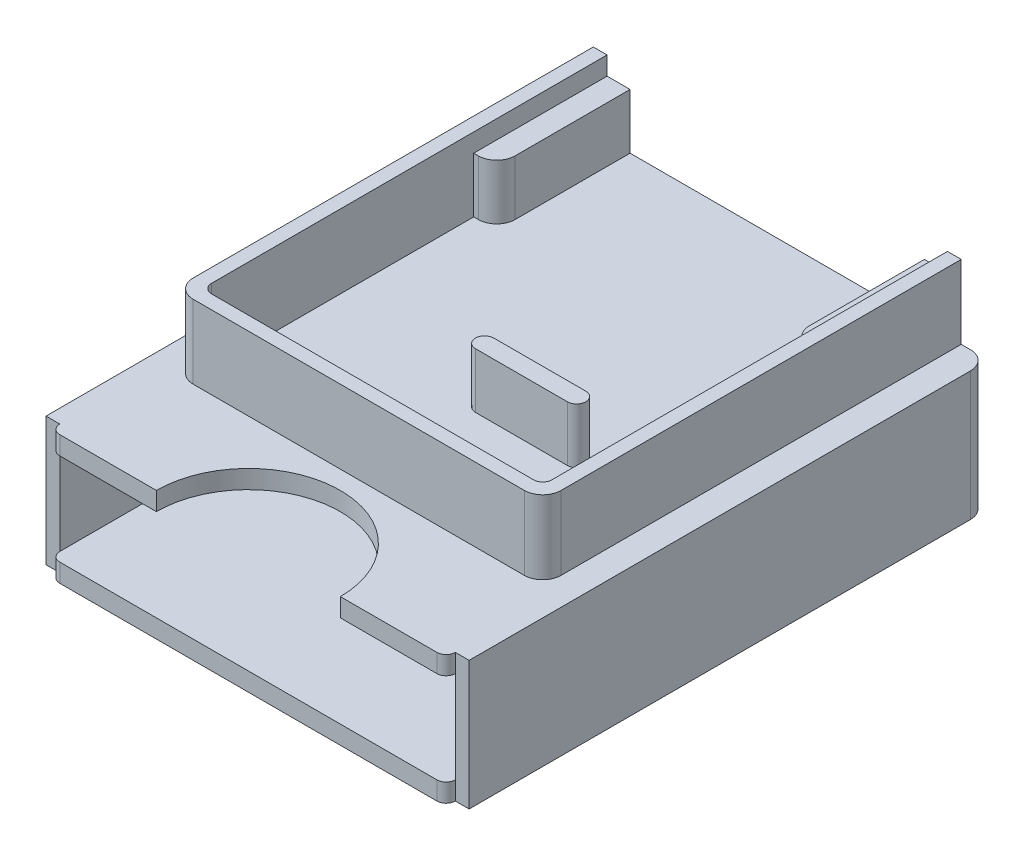
SolidWorks part; units mm, degrees
ref_plane "Front Plane" through (0, 0, 0) normal (0, 0, 1) x (1, 0, 0)
ref_plane "Top Plane" through (0, 0, 0) normal (0, 1, 0) x (1, 0, 0)
ref_plane "Right Plane" through (0, 0, 0) normal (1, 0, 0) x (0, 0, -1)
sketch "Sketch10" plane through (0, 0, 0) normal (0, 1, 0) x (1, 0, 0)
  line L0 (-10.75, -13.5) -> (-11.5, -13.5)
  line L1 (10.5, 14.75) -> (-10.5, 14.75)
  line L2 (11.5, 13.75) -> (11.5, -13.75)
  line L3 (10.5, -14.75) -> (-10.5, -14.75)
  line L4 (-11.5, 13.75) -> (-11.5, -13.75)
  line L5 (4.75, 16.25) -> (-4.75, 16.25)
  line L6 (4.75, 16.25) -> (4.75, 14.75)
  line L7 (10.25, 14) -> (-10.25, 14)
  line L8 (10.75, 13.5) -> (10.75, -13.5)
  line L9 (10.25, -14) -> (-10.25, -14)
  line L10 (-10.75, 13.5) -> (-10.75, -13.5)
  line L11 (4.75, 14.75) -> (-4.75, 14.75)
  line L12 (-4.75, 16.25) -> (-4.75, 14.75)
  line L13 (10.75, -13.5) -> (11.5, -13.5)
  arc A0 (-11.5, -13.75) -> (-10.5, -14.75) centre (-10.5, -13.75) ccw
  arc A1 (11.5, -13.75) -> (10.5, -14.75) centre (10.5, -13.75) cw
  arc A2 (11.5, 13.75) -> (10.5, 14.75) centre (10.5, 13.75) ccw
  arc A3 (-11.5, 13.75) -> (-10.5, 14.75) centre (-10.5, 13.75) cw
  arc A4 (-10.75, 13.5) -> (-10.25, 14) centre (-10.25, 13.5) cw
  arc A5 (-10.75, -13.5) -> (-10.25, -14) centre (-10.25, -13.5) ccw
  arc A6 (10.25, -14) -> (10.75, -13.5) centre (10.25, -13.5) ccw
  arc A7 (10.75, 13.5) -> (10.25, 14) centre (10.25, 13.5) ccw
  point P0 (0, 0)
  point P6 (0, 0)
extrude "Boss-Extrude23" add sketch "Sketch10" along normal blind 1 contours L8 A7 L7 A4 L10 A5 L9 A6 | A3 L4 A0 L3 A1 L2 A2 L1 A7 L8 A6 L9 A5 L10 A4 L7 region at (-11.125, 0, 13.1357) region at (0, 0, 0)
extrude "Boss-Extrude27" add sketch "Sketch10<6>" along normal blind 6 contours A7 L8 L13 L2 A2 L1 A3 L4 L0 L10 A4 L7 region at (-11.125, 0, 13.1357)
sketch "Sketch10<6>" plane through (0, 0, 0) normal (0, 1, 0) x (1, 0, 0) same geometry as "Sketch10"
extrude "Boss-Extrude28" add sketch "Sketch10<7>" along normal blind 1 from offset 6 contours A7 L8 L13 L2 A2 L1 A3 L4 L0 L10 A4 L7 | L8 A7 L7 A4 L10 A5 L9 A6 region at (-11.125, 0, 13.1357) region at (0, 0, 0)
sketch "Sketch10<7>" plane through (0, 0, 0) normal (0, 1, 0) x (1, 0, 0) same geometry as "Sketch10"
sketch "Sketch13" plane through (0, 7, 0) normal (0, 1, 0) x (1, 0, 0)
  line L0 (10.25, -14) -> (-10.25, -14) construction
  line L1 (-5, -14) -> (5, -14)
  arc A0 (5, -14) -> (-5, -14) centre (0, -14) ccw
extrude "Cut-Extrude9" cut sketch "Sketch13" against normal blind 1
sketch "Sketch15" plane through (0, 0, -14.75) normal (0, 0, -1) x (-1, 0, 0)
  line L1 (5, 1) -> (-5, 1)
  line L2 (5, 1) -> (5, 3)
  line L3 (5, 3) -> (-5, 3)
  line L4 (-5, 1) -> (-5, 3)
extrude "Cut-Extrude11" cut sketch "Sketch15" against normal blind 10
sketch "Sketch17" plane through (0, 7, 0) normal (0, 1, 0) x (1, 0, 0)
  line L0 (-9.25, 14.75) -> (-10, 14.75)
  line L1 (-9, 23) -> (9, 23)
  line L2 (-10, 22) -> (-10, -7)
  line L3 (-9, -8) -> (9, -8)
  line L4 (10, 22) -> (10, -7)
  line L5 (-8.75, 22.25) -> (8.75, 22.25)
  line L6 (-9.25, 21.75) -> (-9.25, -6.75)
  line L7 (-8.75, -7.25) -> (8.75, -7.25)
  line L8 (9.25, 21.75) -> (9.25, -6.75)
  line L9 (10.5, 14.75) -> (-10.5, 14.75) construction
  line L10 (9.25, 14.75) -> (10, 14.75)
  arc A0 (-9.25, -6.75) -> (-8.75, -7.25) centre (-8.75, -6.75) ccw
  arc A1 (8.75, -7.25) -> (9.25, -6.75) centre (8.75, -6.75) ccw
  arc A2 (9.25, 21.75) -> (8.75, 22.25) centre (8.75, 21.75) ccw
  arc A3 (-8.75, 22.25) -> (-9.25, 21.75) centre (-8.75, 21.75) ccw
  arc A4 (-10, -7) -> (-9, -8) centre (-9, -7) ccw
  arc A5 (-9, 23) -> (-10, 22) centre (-9, 22) ccw
  arc A6 (9, 23) -> (10, 22) centre (9, 22) cw
  arc A7 (10, -7) -> (9, -8) centre (9, -7) cw
  line M7 (10.5, 14.75) -> (-10.5, 14.75)
extrude "Boss-Extrude30" add sketch "Sketch17" along normal blind 4 contours A7 L4 L8 A1 L7 A0 L6 L2 A4 L3 M7 region at (-9.5529, 7, -4)
sketch "Sketch18" plane through (0, 7, 0) normal (0, 1, 0) x (1, 0, 0)
  line L0 (9, 7.5) -> (9.25, 7.5)
  line L1 (5, -1.1568) -> (0, -1.1568) construction
  line L2 (5, -1.6568) -> (0, -1.6568)
  line L3 (5, -0.6568) -> (0, -0.6568)
  line L4 (9.25, 14.75) -> (9.25, -6.75) construction
  line L5 (9.25, 7.5) -> (9.25, 14.75)
  line L9 (-9.25, 7.5) -> (-9, 7.5)
  line L10 (-9.25, 14.75) -> (-9.25, -6.75) construction
  line L11 (-8, 8.5) -> (-8, 14.75)
  line L12 (9.25, 14.75) -> (-9.25, 14.75) construction
  line L13 (-8, 14.75) -> (-9.25, 14.75)
  line L14 (-9.25, 14.75) -> (-9.25, 7.5)
  line L15 (9.25, 14.75) -> (9.25, -6.75) construction
  line L16 (9.25, 14.75) -> (8, 14.75)
  line L17 (8, 14.75) -> (8, 8.5)
  arc A0 (5, -1.6568) -> (5, -0.6568) centre (5, -1.1568) ccw
  arc A1 (0, -0.6568) -> (0, -1.6568) centre (0, -1.1568) ccw
  arc A2 (9, 7.5) -> (8, 8.5) centre (9, 8.5) cw
  arc A3 (-8, 8.5) -> (-9, 7.5) centre (-9, 8.5) cw
  point P4 (2.5, -1.1568)
  line M1 (9.25, 14.75) -> (-9.25, 14.75)
  line M2 (-9.25, 14.75) -> (-9.25, -6.75)
  line M6 (9.25, -6.75) -> (9.25, 14.75)
extrude "Boss-Extrude31" add sketch "Sketch18" along normal blind 3 contours A3 L11 L9 M1 M2 | A2 L0 L17 M6 M1 | L2 A1 L3 A0 region at (8.6347, 7, -11.2075) region at (-8.6347, 7, -11.2075)
